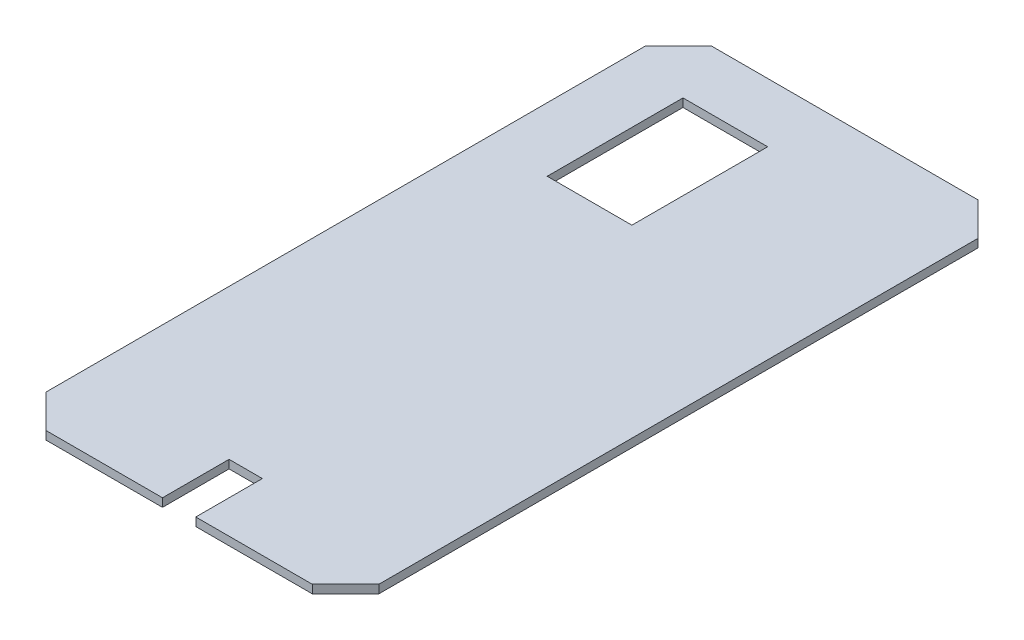
SolidWorks part; units mm, degrees
ref_plane "Front Plane" through (0, 0, 0) normal (0, 0, 1) x (1, 0, 0)
ref_plane "Top Plane" through (0, 0, 0) normal (0, 1, 0) x (1, 0, 0)
ref_plane "Right Plane" through (0, 0, 0) normal (1, 0, 0) x (0, 0, -1)
sketch "Sketch2" plane through (0, 0, 0) normal (0, 1, 0) x (1, 0, 0)
  line L0 (0, 12.7) -> (0, 241.3)
  line L1 (12.7, 254) -> (114.3, 254)
  line L2 (127, 241.3) -> (127, 12.7)
  line L3 (114.3, 0) -> (12.7, 0)
  line L4 (0, 241.3) -> (12.7, 254)
  line L5 (114.3, 254) -> (127, 241.3)
  line L6 (127, 12.7) -> (114.3, 0)
  line L7 (12.7, 0) -> (0, 12.7)
  line L8 (63.5, 254) -> (63.5, -26.6567) construction
  line L10 (0, 127) -> (136.1553, 127) construction
  line L17 (57.15, 25.4) -> (69.85, 25.4)
  line L18 (57.15, 25.4) -> (57.15, 0)
  line L19 (57.15, 0) -> (69.85, 0)
  line L20 (69.85, 25.4) -> (69.85, 0)
  line L21 (57.15, 25.4) -> (69.85, 0) construction
  line L22 (57.15, 0) -> (69.85, 25.4) construction
  line L23 (24.3132, 231.4237) -> (56.6235, 231.4237)
  line L24 (24.3132, 231.4237) -> (24.3132, 179.6184)
  line L25 (24.3132, 179.6184) -> (56.6235, 179.6184)
  line L26 (56.6235, 231.4237) -> (56.6235, 179.6184)
  line L27 (24.3132, 231.4237) -> (56.6235, 179.6184) construction
  line L28 (24.3132, 179.6184) -> (56.6235, 231.4237) construction
  point P0 (63.5, 127)
  point P1 (40.4683, 205.521)
  point P3 (63.5, 12.7)
  point P19 (0, 0)
  point P20 (40.4683, 205.521)
  point P37 (127, 127)
  point P42 (63.5, 0)
  dimension "D14" = 101.6
  dimension "D16" = 12.7
  dimension "D17" = 254
  dimension "D22" = 228.6
  dimension "D36" = 101.6
  dimension "D37" = 228.6
  dimension "D7" = 127
  dimension "D15" = 12.7
  dimension "D4" = 25.4
  dimension "D5" = 12.7
extrude "Boss-Extrude1" add sketch "Sketch2" along normal blind 3.175 contours L7 L3 L6 L2 L5 L1 L4 L0 region at (64.7877, 0, -123.8415)
